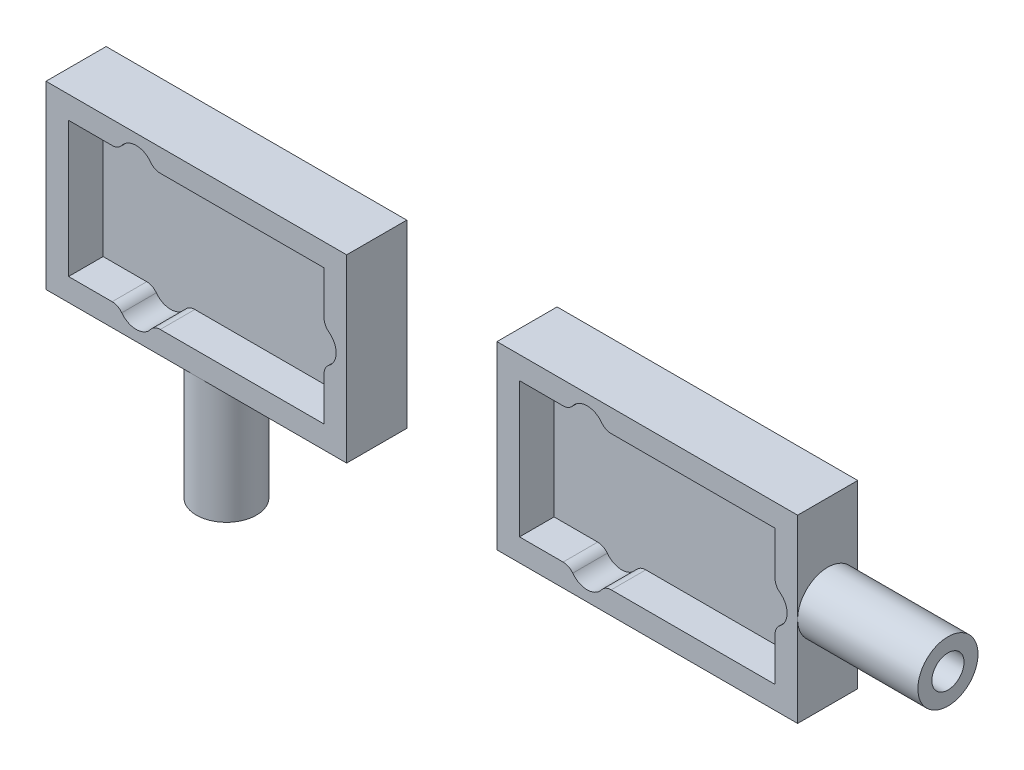
SolidWorks part; units mm, degrees
note: The reader was unsure of these and kept them because the rebuilt part matched: shared geometry of "Sketch8<3>".
ref_plane "Front Plane" through (0, 0, 0) normal (0, 0, 1) x (1, 0, 0)
ref_plane "Top Plane" through (0, 0, 0) normal (0, 1, 0) x (1, 0, 0)
ref_plane "Right Plane" through (0, 0, 0) normal (1, 0, 0) x (0, 0, -1)
sketch "Sketch1" plane through (0, 0, 0) normal (0, 1, 0) x (1, 0, 0)
  circle A0 centre (0, 0) radius 5
  dimension "D1" = 10
extrude "Boss-Extrude1" add sketch "Sketch1" along normal blind 20
sketch "Sketch2" plane through (0, 0, 0) normal (0, -1, 0) x (1, 0, 0)
  circle A0 centre (0, 0) radius 2.65
  dimension "D1" = 5.3
extrude "Cut-Extrude1" cut sketch "Sketch2" against normal blind 12
sketch "Sketch4" plane through (0, 20, 0) normal (0, 1, 0) x (1, 0, 0)
  circle A0 centre (0, 0) radius 6.35
  dimension "D1" = 12.7
extrude "Boss-Extrude2" [suppressed] add sketch "Sketch4" along normal blind 2.54
sketch "Sketch6" [suppressed] plane through (0, 22.54, 0) normal (0, 1, 0) x (1, 0, 0)
  circle A0 centre (0, 0) radius 6.35
  dimension "D1" = 12.7
extrude "Boss-Extrude3" [suppressed] add sketch "Sketch6" against normal blind 3.35
sketch "Sketch7" plane through (0, 0, 0) normal (0, 0, 1) x (1, 0, 0)
  line L0 (0, 0) -> (0, 50) construction
  line L1 (25, 20) -> (-25, 20)
  line L2 (25, 20) -> (25, 50)
  line L3 (25, 50) -> (-25, 50)
  line L4 (-25, 20) -> (-25, 50)
  line L5 (5, 20) -> (-5, 20) construction
  dimension "D1" = 30
  dimension "D2" = 50
extrude "Boss-Extrude4" add sketch "Sketch7" along normal mid plane 10
sketch "Sketch8" plane through (0, 0, 0) normal (0, 0, 1) x (1, 0, 0)
  line L0 (0, 0) -> (0, 50) construction
  line L1 (-20.25, 45.25) -> (-12, 45.25)
  line L2 (-20.25, 45.25) -> (-20.25, 24.75)
  line L3 (-20.25, 24.75) -> (-12, 24.75)
  line L4 (20.25, 45.25) -> (20.25, 37)
  line L5 (25, 50) -> (-25, 50) construction
  line L6 (-25, 35) -> (25, 35) construction
  line L7 (-25, 50) -> (-25, 20) construction
  line L8 (25, 20) -> (25, 50) construction
  line L9 (-10, 47.25) -> (-10, 22.75) construction
  line L10 (10, 45.25) -> (10, 24.75) construction
  line L11 (-8, 45.25) -> (8, 45.25)
  line L12 (12, 45.25) -> (20.25, 45.25)
  line L13 (20.25, 33) -> (20.25, 24.75)
  line L14 (12, 24.75) -> (20.25, 24.75)
  line L15 (-8, 24.75) -> (8, 24.75)
  line L16 (20.25, 37) -> (20.25, 33) construction
  line L17 (-21.25, 46.25) -> (-12.8284, 46.25)
  line L18 (-7.1716, 46.25) -> (10, 46.25)
  line L19 (10, 46.25) -> (21.25, 46.25)
  line L20 (21.25, 46.25) -> (21.25, 37.8284)
  line L21 (21.25, 32.1716) -> (21.25, 23.75)
  line L22 (10, 23.75) -> (21.25, 23.75)
  line L23 (-7.1716, 23.75) -> (10, 23.75)
  line L24 (-21.25, 23.75) -> (-12.8284, 23.75)
  line L25 (-21.25, 46.25) -> (-21.25, 23.75)
  arc A0 (-8, 45.25) -> (-12, 45.25) centre (-10, 45.25) ccw
  arc A1 (-12, 24.75) -> (-8, 24.75) centre (-10, 24.75) ccw
  arc A2 (20.25, 33) -> (20.25, 37) centre (20.25, 35) ccw
  arc A3 (8, 45.25) -> (12, 45.25) centre (10, 45.25) ccw
  arc A4 (12, 24.75) -> (8, 24.75) centre (10, 24.75) ccw
  arc A5 (-7.1716, 46.25) -> (-12.8284, 46.25) centre (-10, 45.25) ccw
  arc A6 (10, 46.25) -> (10, 46.25) centre (10, 45.25) ccw
  arc A7 (21.25, 32.1716) -> (21.25, 37.8284) centre (20.25, 35) ccw
  arc A8 (10, 23.75) -> (10, 23.75) centre (10, 24.75) ccw
  arc A9 (-12.8284, 23.75) -> (-7.1716, 23.75) centre (-10, 24.75) ccw
  point P33 (10, 26.75)
  dimension "D4" = 40.5
  dimension "D5" = 30.25
  dimension "D6" = 2
  dimension "D7" = 1
  dimension "D1" = 20.5
  dimension "D2" = 24.5
  dimension "D3" = 10.25
  dimension "D8" = 2
extrude "Cut-Extrude2" cut sketch "Sketch8" against normal mid plane 1.5 contours L24 A9 L23 L22 L21 A7 L20 L19 L18 A5 L17 L25 L14 A4 L15 A1 L3 L2 L1 A0 L11 A3 L12 L4 A2 L13 | A4 L14 L13 A2 L4 L12 A3 L11 A0 L1 L2 L3 A1 L15
extrude "Cut-Extrude3" cut sketch "Sketch8<3>" along normal blind 12 contours L25 L24 A9 L23 A8 L22 L21 A7 L20 L19 A6 L18 A5 L17
sketch "Sketch8<3>" plane through (0, 0, 0) normal (0, 0, 1) x (1, 0, 0) same geometry as "Sketch8"
move or copy body "Body-Move/Copy1" bodies to move or copy 116 copy yes number of copies 1 translate (75, 0, 0)
sketch "Sketch9" plane through (100, 0, 0) normal (1, 0, 0) x (0, 0, -1)
  line L0 (0, 50) -> (0, 20) construction
  line L1 (-5, 50) -> (5, 50) construction
  line L2 (-5, 20) -> (5, 20) construction
  circle A0 centre (0, 35) radius 5
  circle A1 centre (0, 35) radius 2.675
  dimension "D1" = 10
  dimension "D2" = 5.35
extrude "Boss-Extrude5" add sketch "Sketch9" along normal blind 20 contours A1 L0 | A0 L0 A1 | L0 A1 | L0 A0 A1
sketch "Sketch10" plane through (120, 0, 0) normal (1, 0, 0) x (0, 0, -1)
  circle A0 centre (0, 35) radius 2.675 construction
  circle A1 centre (0, 35) radius 2.675
extrude "Cut-Extrude4" cut sketch "Sketch10" against normal blind 12
sketch "Sketch11" plane through (100, 0, 0) normal (1, 0, 0) x (0, 0, -1)
  line L1 (5, 20) -> (-5, 20)
  line L2 (5, 20) -> (5, 0)
  line L3 (5, 0) -> (-5, 0)
  line L4 (-5, 20) -> (-5, 0)
extrude "Cut-Extrude5" cut sketch "Sketch11" against normal blind 40
fillet "Fillet1" radius 2 6 edges at (-12.8284, 23.75, 2.125) (-7.1716, 23.75, 2.125) (21.25, 32.1716, 2.125) (21.25, 37.8284, 2.125) (-12.8284, 46.25, 2.125) (-7.1716, 46.25, 2.125)
fillet "Fillet2" radius 2 6 edges at (62.1716, 46.25, 2.125) (67.8284, 46.25, 2.125) (96.25, 37.8284, 2.125) (96.25, 32.1716, 2.125) (67.8284, 23.75, 2.125) (62.1716, 23.75, 2.125)
